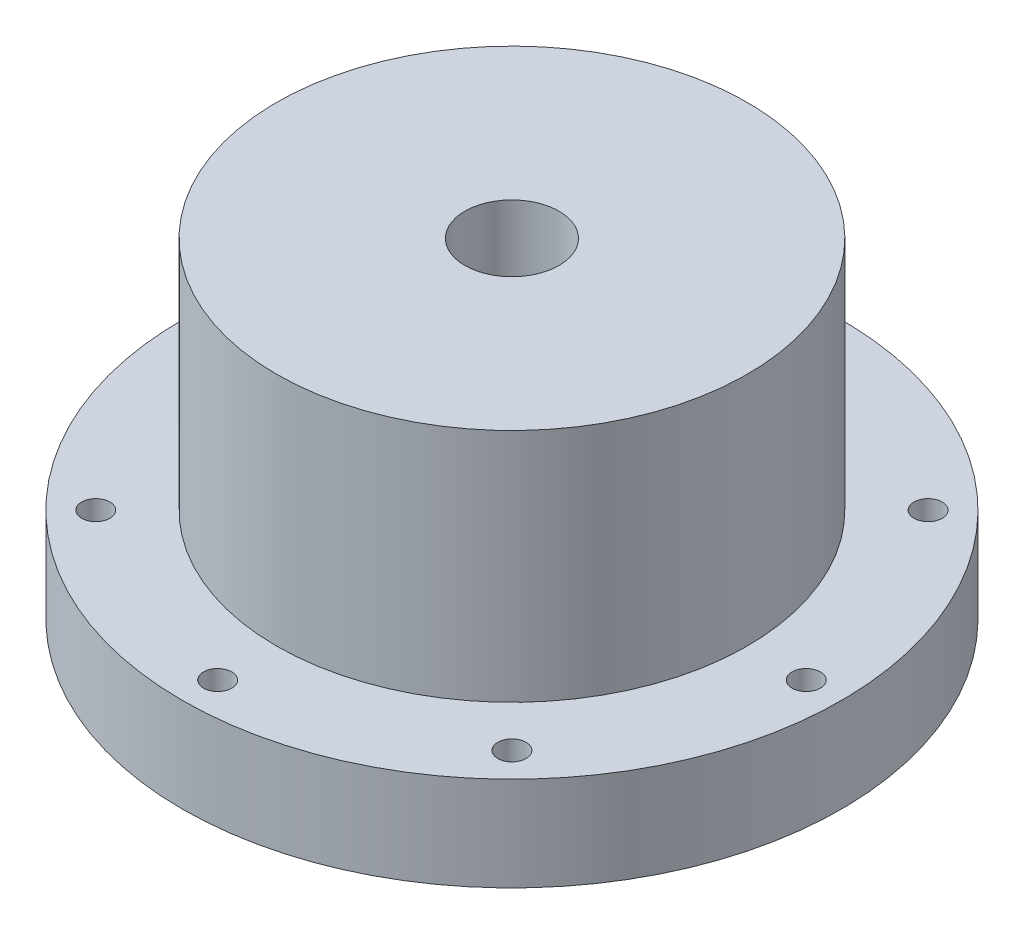
SolidWorks part; units mm, degrees
ref_plane "Front Plane" through (0, 0, 0) normal (0, 0, 1) x (1, 0, 0)
ref_plane "Top Plane" through (0, 0, 0) normal (0, 1, 0) x (1, 0, 0)
ref_plane "Right Plane" through (0, 0, 0) normal (1, 0, 0) x (0, 0, -1)
sketch "Sketch1" plane through (0, 0, 0) normal (0, 1, 0) x (1, 0, 0)
  circle A0 centre (0, 0) radius 70
  circle A1 centre (0, 0) radius 10
  circle A2 centre (0, 0) radius 50
  dimension "D1" = 140
  dimension "D2" = 100
  dimension "D3" = 20
extrude "Boss-Extrude1" add sketch "Sketch1" along normal blind 20 contours A0 A2 | A2 A1 region at (-68.0201, 0, 0) region at (-48.5858, 0, 0)
extrude "Boss-Extrude2" add sketch "Sketch1<3>" along normal blind 70 contours A2 A1 region at (-48.5858, 0, 0)
sketch "Sketch1<3>" plane through (0, 0, 0) normal (0, 1, 0) x (1, 0, 0) same geometry as "Sketch1"
sketch "Sketch2" plane through (0, 0, 0) normal (0, -1, 0) x (1, 0, 0)
  line L0 (0, 0) -> (0, 62.5)
  circle A0 centre (0, 0) radius 62.5
  circle A1 centre (0, 62.5) radius 3
  circle A2 centre (44.1942, 44.1942) radius 3
  circle A3 centre (62.5, 0) radius 3
  circle A4 centre (44.1942, -44.1942) radius 3
  circle A5 centre (0, -62.5) radius 3
  circle A6 centre (-44.1942, -44.1942) radius 3
  circle A7 centre (-62.5, 0) radius 3
  circle A8 centre (-44.1942, 44.1942) radius 3
  dimension "D1" = 125
  dimension "D2" = 6
  dimension "D3" = 8
extrude "Cut-Extrude1" cut sketch "Sketch2" against normal through all contours A0 A8 | A0 A8 | A0 A1 | L0 A1 A0 | A0 A1 L0 | A0 A7 | A0 A7 | A0 A5 | A0 A5 | A6 | A4 | A3 | A2 region at (-1.2632, 0, 61.2139) region at (1.2632, 0, 61.2139) region at (0, 0, 63.7602) region at (-43.2847, 0, 43.2847) region at (-45.0853, 0, 45.0853) region at (-61.2139, 0, 0) region at (-63.7602, 0, 0) region at (0, 0, -61.2139) region at (0, 0, -63.7602)
